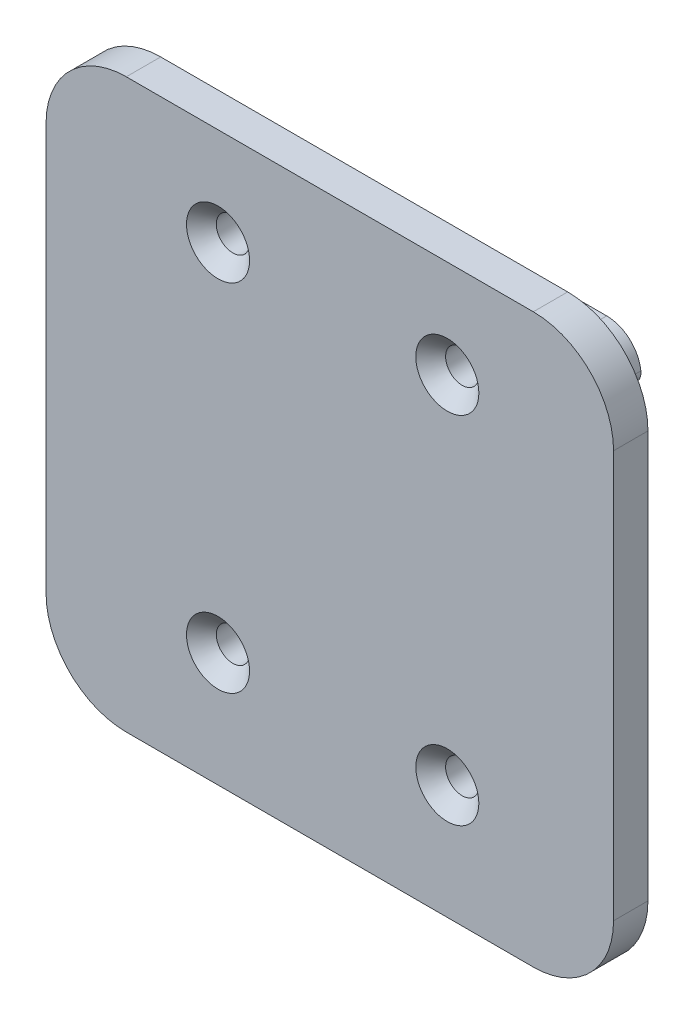
SolidWorks part; units mm, degrees
ref_plane "前视基准面" through (0, 0, 0) normal (0, 0, 1) x (1, 0, 0)
ref_plane "上视基准面" through (0, 0, 0) normal (0, 1, 0) x (1, 0, 0)
ref_plane "右视基准面" through (0, 0, 0) normal (1, 0, 0) x (0, 0, -1)
sketch "草图1" plane through (0, 0, 0) normal (0, 0, 1) x (1, 0, 0)
  line L1 (96.518, -36.187) -> (61.018, -36.187)
  line L2 (103.518, -43.187) -> (103.518, -78.687)
  line L3 (96.518, -85.687) -> (61.018, -85.687)
  line L4 (54.018, -43.187) -> (54.018, -78.687)
  arc A0 (61.018, -85.687) -> (54.018, -78.687) centre (61.018, -78.687) cw
  arc A1 (103.518, -78.687) -> (96.518, -85.687) centre (96.518, -78.687) cw
  arc A2 (96.518, -36.187) -> (103.518, -43.187) centre (96.518, -43.187) cw
  arc A3 (61.018, -36.187) -> (54.018, -43.187) centre (61.018, -43.187) ccw
  point P10 (103.518, -36.187)
  point P13 (54.018, -36.187)
  dimension "D2" = 7
  dimension "D1" = 49.5
  dimension "D3" = 54.018
  dimension "D4" = 36.187
extrude "凸台-拉伸1" add sketch "草图1" along normal blind 3 contours L1 A3 L4 A0 L3 A1 L2 A2
sketch "草图3" plane through (0, 0, 0) normal (0, 0, -1) x (-1, 0, 0)
  line L0 (-103.518, -43.187) -> (-103.518, -78.687) construction
  line L1 (-99.018, -56.687) -> (-58.518, -56.687)
  line L2 (-99.018, -56.687) -> (-99.018, -59.687)
  line L3 (-99.018, -59.687) -> (-58.518, -59.687)
  line L4 (-58.518, -56.687) -> (-58.518, -59.687)
  line L5 (-54.018, -43.187) -> (-54.018, -78.687) construction
  line L7 (-99.018, -58.187) -> (-58.518, -58.187) construction
  line L8 (-96.518, -36.187) -> (-61.018, -36.187) construction
  dimension "D1" = 4.5
  dimension "D2" = 4.5
  dimension "D3" = 22
  dimension "D4" = 3
extrude "凸台-拉伸3" add sketch "草图3" along normal blind 4.4 contours L3 L4 L1 L2
sketch "草图4" plane through (0, 0, 0) normal (0, 0, -1) x (-1, 0, 0)
  line L0 (-79.018, -36.207) -> (-79.018, -84.187)
  line L1 (-103.518, -43.187) -> (-103.518, -78.687) construction
  line L2 (-54.018, -43.187) -> (-54.018, -78.687) construction
  line L3 (-89.018, -44.697) -> (-69.018, -44.697)
  line L6 (-89.018, -75.697) -> (-69.018, -75.697)
  line L7 (-89.018, -75.697) -> (-89.018, -44.697)
  line L8 (-89.018, -44.697) -> (-69.018, -44.697)
  line L9 (-69.018, -75.697) -> (-69.018, -44.697)
  line L10 (-89.018, -75.697) -> (-69.018, -44.697) construction
  line L11 (-89.018, -44.697) -> (-69.018, -75.697) construction
  line L12 (-98.518, -40.697) -> (-59.018, -40.697)
  line L13 (-89.018, -75.697) -> (-69.018, -75.697)
  line L17 (-98.518, -40.697) -> (-59.018, -40.697)
  line L18 (-98.518, -40.697) -> (-98.518, -44.697)
  line L19 (-59.018, -40.697) -> (-59.018, -44.697)
  line L20 (-98.518, -44.697) -> (-59.018, -44.697)
  line L21 (-89.018, -60.197) -> (-69.018, -60.197) construction
  line L22 (-98.518, -75.697) -> (-59.018, -75.697)
  line L23 (-59.018, -79.697) -> (-59.018, -75.697)
  line L24 (-98.518, -79.697) -> (-59.018, -79.697)
  line L25 (-98.518, -79.697) -> (-98.518, -75.697)
  line L26 (-54.018, -43.187) -> (-54.018, -78.687) construction
  line L27 (-96.518, -36.187) -> (-61.018, -36.187) construction
  line L28 (-96.518, -85.687) -> (-61.018, -85.687) construction
  circle A0 centre (-89.018, -44.697) radius 1.3
  circle A1 centre (-69.018, -44.697) radius 1.3
  circle A2 centre (-89.018, -75.697) radius 1.3
  circle A3 centre (-69.018, -75.697) radius 1.3
  circle A4 centre (-89.018, -44.697) radius 2.5
  circle A5 centre (-69.018, -44.697) radius 2.5
  circle A6 centre (-69.018, -75.697) radius 2.5
  circle A7 centre (-89.018, -75.697) radius 2.5
  point P6 (-79.018, -60.197)
  point P8 (-79.018, -60.197)
  point P9 (-79.018, -60.197)
  dimension "D3" = 2.6
  dimension "D1" = 31
  dimension "D2" = 20
  dimension "D4" = 4
  dimension "D5" = 5
  dimension "D7" = 25
  dimension "D8" = 25
  dimension "D9" = 5
  dimension "D10" = 8.51
  dimension "D11" = 9.99
  dimension "D6" = 1.2
extrude "凸台-拉伸6" add sketch "草图4" along normal up to surface (4.4 mm away) contours A4 L3 L0 L12 L18 L20 | A5 L20 L19 L12 L0 L3 | L7 A4 L20 A0 | L20 A4 L7 A0 | L20 A4 A0 | L20 A5 A1 | L20 A5 L9 A1 | L9 A5 L20 A1 | L22 A6 L9 A3 | L22 A6 A3 | A6 L6 L0 L24 L23 L22 | L9 A6 L22 A3 | A7 L22 L25 L24 L0 L6 | L22 A7 A2 | L22 A7 L7 A2 | L7 A7 L22 A2 up to face at (78.768, -58.187, -4.4)
sketch "草图2" plane through (0, 0, 0) normal (0, 0, -1) x (-1, 0, 0)
  line L0 (-54.018, -43.187) -> (-54.018, -78.687) construction
  line L1 (-54.018, -44.697) -> (-56.518, -44.697)
  line L2 (-54.018, -44.697) -> (-54.018, -56.687)
  line L3 (-54.018, -56.687) -> (-56.518, -56.687)
  line L4 (-56.518, -44.697) -> (-56.518, -56.687)
  line L5 (-99.018, -56.687) -> (-58.518, -56.687) construction
  line L7 (-66.518, -44.697) -> (-59.018, -44.697) construction
  dimension "D1" = 2.5
extrude "凸台-拉伸2" add sketch "草图2" along normal blind 1.8
fillet "圆角1" radius 3 4 edges at (59.018, -79.697, -2.2) (98.518, -79.697, -2.2) (98.518, -40.697, -2.2) (59.018, -40.697, -2.2)
fillet "圆角2" radius 1.2 7 edges at (91.518, -75.697, -2.2) (98.518, -75.697, -2.2) (66.518, -75.697, -2.2) (59.018, -75.697, -2.2) (91.518, -44.697, -2.2) (98.518, -44.697, -2.2) (66.518, -44.697, -2.2)
hole_wizard "M2.5 平头机械螺钉的锥形沉头孔1" positions "草图6" profile "草图7" countersink size "M2.5" standard "ANSI Metric" end condition through all
sketch "草图6" plane through (0, 0, 3) normal (0, 0, 1) x (1, 0, 0)
  point P0 (69.018, -44.697)
  point P3 (69.018, -75.697)
  point P6 (89.018, -75.697)
  point P9 (89.018, -44.697)
sketch "草图7" plane through (69.018, -44.697, 3) normal (1, 0, 0) x (0, -1, 0)
  line L0 (0, 0) -> (0, 7.4)
  line L1 (0, 7.4) -> (1.45, 7.4)
  line L2 (1.45, 7.4) -> (1.45, 1.3)
  line L3 (1.45, 1.3) -> (2.75, 0)
  line L5 (2.75, 0) -> (0, 0)
  line L6 (-1.45, 1.3) -> (-2.75, 0) construction
  line L11 (0, -6.35) -> (0, 107.95) construction
  dimension "通孔孔直径" = 2.9
  dimension "通孔孔深度" = 7.4
  dimension "近端锥形沉头孔直径" = 5.5
  dimension "近端锥形沉头孔角度" = 90
sketch "草图8" plane through (54.018, 0, 0) normal (-1, 0, 0) x (0, 0, 1)
  line L0 (-1.8, -56.687) -> (-1.8, -44.697) construction
  line L1 (-6.6, -58.197) -> (3, -58.197)
  line L2 (-6.6, -58.197) -> (-6.6, -43.187)
  line L3 (-6.6, -43.187) -> (3, -43.187)
  line L4 (3, -58.197) -> (3, -43.187)
  line L5 (-6.6, -58.197) -> (3, -43.187) construction
  line L6 (-6.6, -43.187) -> (3, -58.197) construction
  line L7 (3, -43.187) -> (3, -78.687) construction
  line L8 (-6.6, -43.187) -> (3, -43.187)
  line L9 (-6.6, -43.187) -> (-6.6, -36.187)
  line L10 (-6.6, -36.187) -> (3, -36.187)
  line L11 (3, -43.187) -> (3, -36.187)
  line L12 (-6.6, -58.197) -> (3, -58.197)
  line L13 (-6.6, -58.197) -> (-6.6, -59.197)
  line L14 (-6.6, -59.197) -> (3, -59.197)
  line L15 (3, -58.197) -> (3, -59.197)
  point P0 (-1.8, -50.692)
  dimension "D1" = 1
chamfer "倒角3" distance 1 angle 45 4 edges at (59.018, -44.697, -2.2) (56.518, -44.697, -0.9) (56.518, -56.687, -0.9) (58.518, -56.687, -2.2)
